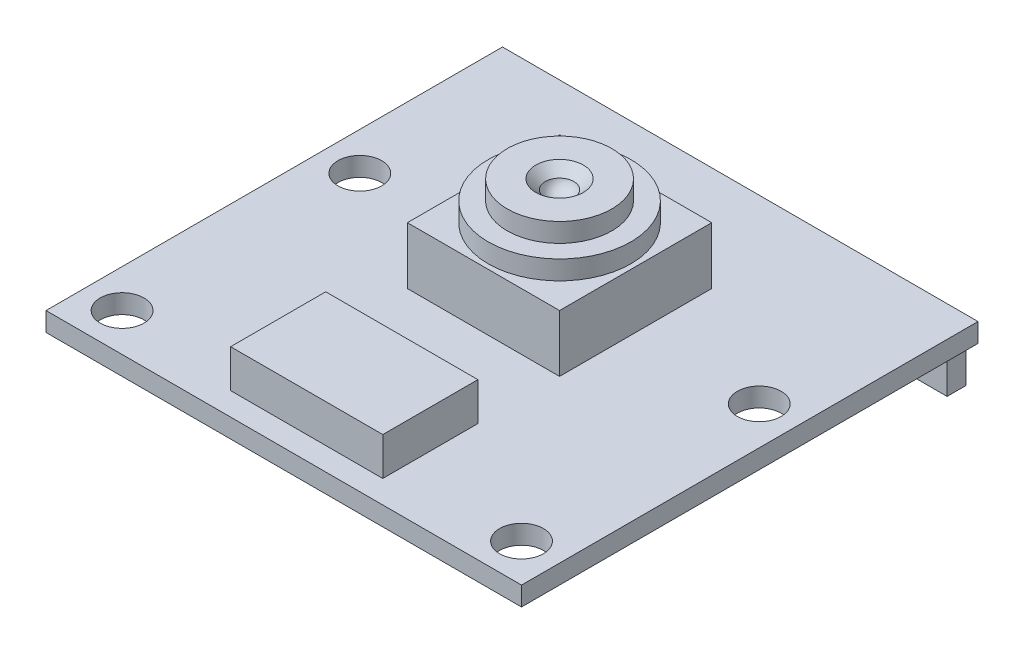
SolidWorks part; units mm, degrees
ref_plane "Front Plane" through (0, 0, 0) normal (0, 0, 1) x (1, 0, 0)
ref_plane "Top Plane" through (0, 0, 0) normal (0, 1, 0) x (1, 0, 0)
ref_plane "Right Plane" through (0, 0, 0) normal (1, 0, 0) x (0, 0, -1)
sketch "Sketch1" plane through (0, 0, 0) normal (0, 1, 0) x (1, 0, 0)
  line L1 (-12.5, 12) -> (12.5, 12)
  line L2 (-12.5, 12) -> (-12.5, -12)
  line L3 (-12.5, -12) -> (12.5, -12)
  line L4 (12.5, 12) -> (12.5, -12)
  point P0 (0, 0)
extrude "Boss-Extrude1" add sketch "Sketch1" along normal blind 1
sketch "Sketch2" plane through (0, 1, 0) normal (0, 1, 0) x (1, 0, 0)
  circle A0 centre (10.5, -10) radius 1.15
  circle A1 centre (-10.5, -10) radius 1.15
  circle A2 centre (-10.5, 2.5) radius 1.15
  circle A3 centre (10.5, 2.5) radius 1.15
extrude "Cut-Extrude1" cut sketch "Sketch2" against normal blind 1
sketch "Sketch3" plane through (0, 1, 0) normal (0, 1, 0) x (1, 0, 0)
  line L3 (-4, -5.7933) -> (4, -5.7933)
  line L4 (-4, -5.7933) -> (-4, -10.7933)
  line L5 (-4, -10.7933) -> (4, -10.7933)
  line L6 (4, -5.7933) -> (4, -10.7933)
extrude "Boss-Extrude2" add sketch "Sketch3" along normal blind 2
sketch "Sketch4" plane through (0, 1, 0) normal (0, 1, 0) x (1, 0, 0)
  line L2 (-4, 6.5) -> (4, 6.5)
  line L3 (-4, 6.5) -> (-4, -1.5)
  line L4 (-4, -1.5) -> (4, -1.5)
  line L5 (4, 6.5) -> (4, -1.5)
  point P4 (0, 2.5)
extrude "Boss-Extrude3" add sketch "Sketch4" along normal blind 3
sketch "Sketch5" plane through (0, 4, 0) normal (0, 1, 0) x (1, 0, 0)
  circle A0 centre (0, 2.5) radius 3.75
extrude "Boss-Extrude4" add sketch "Sketch5" along normal blind 1
sketch "Sketch6" plane through (0, 5, 0) normal (0, 1, 0) x (1, 0, 0)
  circle A1 centre (0, 2.5) radius 2.75
extrude "Boss-Extrude5" add sketch "Sketch6" along normal blind 1
sketch "Sketch7" plane through (0, 6, 0) normal (0, 1, 0) x (1, 0, 0)
  circle A0 centre (0, 2.5) radius 0.75
extrude "Cut-Extrude3" cut sketch "Sketch7" against normal blind 1
chamfer "Chamfer1" distance 0.5 angle 45 1 edges at (0, 6, -1.75)
fillet "Fillet2" radius 0.7 1 edges at (0, 5, -1.75)
sketch "Sketch8" plane through (0, 0, 0) normal (0, -1, 0) x (1, 0, 0)
  line L0 (10.5, -11.875) -> (12, -11.875)
  line L2 (12, -11.875) -> (12, -10.875)
  line L3 (10.5, -11.875) -> (-10.5, -11.875)
  line L4 (10.5, -10.875) -> (10.5, -6.625)
  line L5 (10.5, -6.625) -> (-10.5, -6.625)
  line L7 (12, -10.875) -> (10.5, -10.875)
  line L8 (-10.5, -11.875) -> (-12, -11.875)
  line L9 (-12, -11.875) -> (-12, -10.875)
  line L10 (-12, -10.875) -> (-10.5, -10.875)
  line L11 (-10.5, -10.875) -> (-10.5, -6.625)
extrude "Boss-Extrude6" add sketch "Sketch8" along normal blind 2
sketch "Sketch9" plane through (0, -2, 0) normal (0, -1, 0) x (1, 0, 0)
  line L1 (12, -11.875) -> (-12, -11.875)
  line L2 (12, -11.875) -> (12, -10.875)
  line L3 (12, -10.875) -> (-12, -10.875)
  line L4 (-12, -11.875) -> (-12, -10.875)
extrude "Boss-Extrude7" add sketch "Sketch9" along normal blind 0.1
